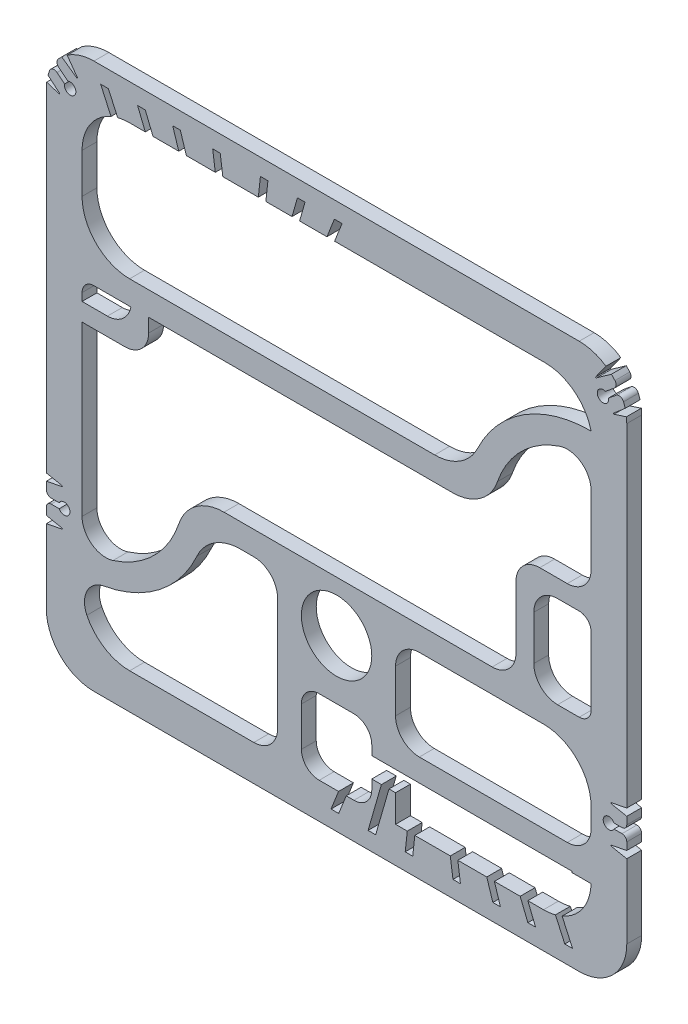
SolidWorks part; units mm, degrees
ref_plane "Front Plane" through (0, 0, 0) normal (0, 0, 1) x (1, 0, 0)
ref_plane "Top Plane" through (0, 0, 0) normal (0, 1, 0) x (1, 0, 0)
ref_plane "Right Plane" through (0, 0, 0) normal (1, 0, 0) x (0, 0, -1)
sketch "Sketch1" plane through (0, 0, 0) normal (0, 0, 1) x (1, 0, 0)
  line L0 (44.642, 21.8842) -> (44.642, 18.0742) construction
  line L1 (-10.1934, 21.8842) -> (51.7832, 21.8842)
  line L2 (-10.1934, 21.8842) -> (-10.1934, -36.406)
  line L3 (-10.1934, -36.406) -> (51.7832, -36.406)
  line L4 (51.7832, 21.8842) -> (51.7832, -36.406)
  line L5 (47.9732, -32.596) -> (-6.3834, -32.596)
  line L6 (47.9732, -32.596) -> (47.9732, 18.0742)
  line L7 (47.9732, 18.0742) -> (-6.3834, 18.0742)
  line L8 (-6.3834, -32.596) -> (-6.3834, 18.0742)
  line L9 (44.642, 19.9792) -> (-35.1587, 19.9792) construction
  line L10 (-6.3834, -31.0517) -> (-10.1934, -31.0517) construction
  line L11 (-8.2884, -31.0517) -> (-8.2884, 6.9585) construction
  line L12 (20.6521, 19.9792) -> (21.1982, 19.9792) construction
  line L14 (3.0779, -32.596) -> (3.0779, -36.406) construction
  line L15 (3.0779, -34.501) -> (37.3423, -34.501) construction
  line L16 (47.9732, -22.563) -> (47.9732, 12.9942) construction
  line L17 (51.7832, 15.2205) -> (47.9732, 15.2205) construction
  line L18 (49.8782, 15.2205) -> (49.8782, -0.9437) construction
  line L20 (20.9378, -34.501) -> (20.3916, -34.501) construction
  line L21 (-6.3834, 8.0412) -> (-6.3834, -27.516) construction
  dimension "D1" = 3.81
  dimension "D2" = 3.81
extrude "Boss-Extrude1" add sketch "Sketch1" along normal blind 1.5875
sketch "Sketch2" plane through (0, 0, 0) normal (0, 0, -1) x (-1, 0, 0)
  line L0 (-47.9732, -32.596) -> (-47.9732, 18.0742) construction
  line L1 (-34.8696, 3.653) -> (6.3834, 3.653)
  line L2 (-47.9732, 3.653) -> (-47.9732, 0.8076)
  line L3 (-37.4096, 1.113) -> (6.3834, 1.113)
  line L4 (6.3834, 3.653) -> (6.3834, 1.113)
  line L5 (6.3834, 18.0742) -> (6.3834, -32.596) construction
  line L6 (-33.4496, 1.113) -> (-36.4496, 1.113) construction
  line L7 (1.2504, -12.887) -> (-36.4496, -12.887) construction
  line L8 (-47.9732, -15.427) -> (-6.8239, -15.427)
  line L9 (-47.9732, -15.427) -> (-47.9732, -12.887)
  line L10 (-47.9732, -12.887) -> (-4.5259, -12.887)
  line L11 (1.357, -21.2563) -> (14.2432, -21.2563) construction
  line L12 (6.3834, -23.7963) -> (6.3834, -26.3363)
  line L13 (-47.9732, 14.2166) -> (-47.9732, 11.6766)
  arc A0 (-47.9732, 11.6766) -> (-37.4096, 1.113) centre (-47.9732, 1.113) cw
  arc A1 (-47.9732, 14.2166) -> (-34.8696, 3.653) centre (-47.9732, 0.8076) cw
  arc A2 (6.3834, -23.7963) -> (-4.5259, -12.887) centre (6.3834, -12.887) cw
  arc A3 (-6.8239, -15.427) -> (6.3834, -26.3363) centre (6.3834, -12.887) ccw
  circle A5 centre (1.357, -18.2591) radius 2.9972 construction
  line M5 (-47.9732, -32.596) -> (-47.9732, 18.0742)
  line M7 (6.3834, 18.0742) -> (6.3834, -32.596)
  dimension "D5" = 2.54
  dimension "D1" = 2.54
  dimension "D2" = 2.54
  dimension "D3" = 2.54
  dimension "D4" = 2.54
  dimension "D6" = 2.54
  dimension "D7" = 2.54
extrude "Boss-Extrude2" add sketch "Sketch2" against normal up to surface (1.5875 mm away) contours A1 A0 L3 L1 M5 M7 | L10 L8 M5 M7 region at (14.2431, 3.0939, 0) region at (-5.8234, -25.0663, 0) up to face at (20.7949, -7.2609, 1.5875)
sketch "Sketch3" plane through (0, 0, 0) normal (0, 0, -1) x (-1, 0, 0)
  line L0 (-47.9732, -1.1649) -> (-39.9496, -1.1649)
  line L1 (-47.9732, -12.887) -> (-47.9732, 11.6766) construction
  line L2 (-39.9496, -4.387) -> (-39.9496, -11.387) construction
  line L3 (-39.9496, -1.1649) -> (-39.9496, -12.887)
  line L4 (-47.9732, -12.887) -> (-4.5259, -12.887) construction
  line L5 (-39.9496, -12.887) -> (-41.8546, -12.887)
  line L6 (-41.8546, -12.887) -> (-41.8546, -3.0699)
  line L7 (-41.8546, -3.0699) -> (-47.9732, -3.0699)
  line L8 (-47.9732, -3.0699) -> (-47.9732, -1.1649)
  line L9 (-42.9468, 0.7401) -> (-53.4831, 0.7401) construction
  line L10 (-0.7296, 1.113) -> (-0.7296, -2.887)
  line L11 (-37.4096, 1.113) -> (6.3834, 1.113) construction
  line L12 (-1.9996, -2.887) -> (1.2504, -2.887) construction
  line L13 (-0.7296, -2.887) -> (6.3834, -2.887)
  line L14 (6.3834, 1.113) -> (6.3834, -23.7963) construction
  line L15 (6.3834, -2.887) -> (6.3834, -0.982)
  line L16 (6.3834, -0.982) -> (1.1754, -0.982)
  line L17 (1.1754, -0.982) -> (1.1754, 1.113)
  line L18 (1.1754, 1.113) -> (-0.7296, 1.113)
  circle A0 centre (-42.9468, 3.7373) radius 2.9972 construction
  dimension "D1" = 1.905
  dimension "D2" = 1.905
  dimension "D3" = 1.905
  dimension "D4" = 1.905
  dimension "D5" = 1.27
  dimension "D6" = 1.905
extrude "Boss-Extrude3" add sketch "Sketch3" against normal up to surface (1.5875 mm away) up to face at (20.8645, -5.9566, 1.5875)
fillet "Fillet1" radius 5.08 4 edges at (51.7832, -36.406, 0.7937) (-10.1934, -36.406, 0.7937) (-10.1934, 21.8842, 0.7937) (51.7832, 21.8842, 0.7937)
fillet "Fillet2" radius 5.08 10 edges at (6.8239, -15.427, 0.7937) (47.9732, -15.427, 0.7937) (47.9732, -32.596, 0.7937) (-6.3834, -32.596, 0.7937) (34.8696, 3.653, 0.7938) (-6.3834, 3.653, 0.7937) (47.9732, 18.0742, 0.7937) (-6.3834, 18.0742, 0.7937) (4.5259, -12.887, 0.7937) (37.4096, 1.113, 0.7938)
fillet "Fillet3" radius 2.54 10 edges at (41.8546, -3.0699, 0.7938) (39.9496, -12.887, 0.7938) (41.8546, -12.887, 0.7938) (39.9496, -1.1649, 0.7938) (47.9732, -1.1649, 0.7938) (-1.1754, -0.982, 0.7938) (0.7296, -2.887, 0.7938) (47.9732, 11.6766, 0.7937) (-6.3834, -26.3363, 0.7937) (-6.3834, -23.7963, 0.7937)
fillet "Fillet4" radius 1.27 3 edges at (47.9732, -12.887, 0.7937) (47.9732, -3.0699, 0.7938) (-6.3834, 1.113, 0.7938)
sketch "Sketch5" plane through (0, 0, 0) normal (0, 0, -1) x (-1, 0, 0)
  line L0 (-42.8932, -15.427) -> (-10.5066, -15.427) construction
  line L1 (-27.0941, -15.427) -> (-14.4957, -15.427)
  line L2 (-27.0941, -15.427) -> (-27.0941, -32.596)
  line L3 (-27.0941, -32.596) -> (-14.4957, -32.596)
  line L4 (-14.4957, -15.427) -> (-14.4957, -32.596)
  line L5 (1.3034, -32.596) -> (-42.8932, -32.596) construction
  line L6 (-24.5541, -18.2972) -> (-27.0941, -18.2972) construction
  line L9 (-17.0357, -18.2972) -> (-14.4957, -18.2972) construction
  circle A1 centre (-20.7949, -18.2972) radius 3.7592 construction
  dimension "D1" = 2.54
extrude "Boss-Extrude4" add sketch "Sketch5" against normal up to surface (1.5875 mm away) up to face at (-4.5227, -0.0173, 1.5875)
sketch "Sketch6" plane through (0, 0, 0) normal (0, 0, -1) x (-1, 0, 0)
  circle A0 centre (-20.7949, -18.2972) radius 3.7592 construction
  circle A1 centre (-20.7949, -18.2972) radius 3.7592
extrude "Cut-Extrude2" cut sketch "Sketch6" against normal up to surface (1.5875 mm away) up to face at (4.768, -24.4396, 1.5875)
sketch "Sketch7" plane through (0, 0, 0) normal (0, 0, -1) x (-1, 0, 0)
  line L0 (-27.0941, -15.427) -> (-27.0941, -32.596) construction
  line L1 (-24.5541, -24.5964) -> (-17.0357, -24.5964)
  line L2 (-24.5541, -24.5964) -> (-24.5541, -32.596)
  line L3 (-24.5541, -32.596) -> (-17.0357, -32.596)
  line L4 (-17.0357, -24.5964) -> (-17.0357, -32.596)
  line L5 (-14.4957, -32.596) -> (-14.4957, -15.427) construction
  line L6 (1.3034, -32.596) -> (-14.4957, -32.596) construction
  line L7 (-20.7949, -22.0564) -> (-6.5424, -22.0564) construction
  line L8 (-20.7949, -22.0564) -> (-20.7949, -21.3452) construction
  circle A0 centre (-20.7949, -18.2972) radius 3.7592 construction
  dimension "D1" = 2.54
  dimension "D2" = 2.54
  dimension "D3" = 2.54
extrude "Cut-Extrude3" cut sketch "Sketch7" against normal up to surface (1.5875 mm away) up to face at (24.5541, -18.2972, 1.5875)
fillet "Fillet5" radius 1.905 4 edges at (24.5541, -32.596, 0.7937) (17.0357, -32.596, 0.7938) (17.0357, -24.5964, 0.7938) (24.5541, -24.5964, 0.7938)
sketch "Sketch8" plane through (0, 0, 0) normal (0, 0, -1) x (-1, 0, 0)
  line L0 (-47.9732, -27.516) -> (-47.9732, -20.507) construction
  line L1 (-47.9732, -25.103) -> (-27.0941, -25.103)
  line L2 (-47.9732, -25.103) -> (-47.9732, -27.643)
  line L3 (-47.9732, -27.643) -> (-27.0941, -27.643)
  line L4 (-27.0941, -25.103) -> (-27.0941, -27.643)
  line L5 (-27.0941, -15.427) -> (-27.0941, -32.596) construction
  line L6 (-45.7916, -27.643) -> (-20.3916, -27.643) construction
  dimension "D1" = 2.54
extrude "Boss-Extrude5" add sketch "Sketch8" against normal up to surface (1.5875 mm away) up to face at (20.7949, -28.5962, 1.5875)
fillet "Fillet6" radius 2.54 5 edges at (27.0941, -15.427, 0.7937) (14.4957, -15.427, 0.7937) (14.4957, -32.596, 0.7937) (27.0941, -25.103, 0.7937) (47.9732, -25.103, 0.7937)
sketch "Sketch4" plane through (0, 0, 0) normal (0, 0, -1) x (-1, 0, 0)
  line L0 (3.2504, -2.887) -> (4.7504, -4.387) construction
  line L1 (4.7504, -11.387) -> (3.2504, -12.887) construction
  line L2 (3.2504, -2.887) -> (4.7504, -4.387)
  line L3 (4.7504, -11.387) -> (3.2504, -12.887)
  line L4 (4.7504, -4.387) -> (4.7504, -11.387) construction
  line L5 (4.7504, -4.387) -> (4.7504, -11.387)
  line L6 (3.2504, -2.887) -> (3.2504, -12.887)
  line L32 (4.2018, 13.1212) -> (4.2018, 15.0262)
  line L33 (4.2018, 15.0262) -> (1.9539, 15.0262)
  line L34 (1.9539, 15.0262) -> (4.2018, 19.9792)
  line L35 (4.2018, 19.9792) -> (3.6556, 19.9792)
  line L36 (3.6556, 19.9792) -> (1.4078, 15.0262)
  line L37 (1.4078, 15.0262) -> (-1.7417, 15.0262)
  line L38 (-1.7417, 15.0262) -> (0.2648, 19.9792)
  line L39 (0.2648, 19.9792) -> (-0.2814, 19.9792)
  line L40 (-0.2814, 19.9792) -> (-2.2879, 15.0262)
  line L41 (-2.2879, 15.0262) -> (-5.0437, 15.0262)
  line L42 (-5.0437, 15.0262) -> (-3.469, 19.9792)
  line L43 (-3.469, 19.9792) -> (-4.0152, 19.9792)
  line L44 (-4.0152, 19.9792) -> (-5.5899, 15.0262)
  line L45 (-5.5899, 15.0262) -> (-8.3965, 15.0262)
  line L46 (-8.3965, 15.0262) -> (-7.7108, 19.9792)
  line L47 (-7.7108, 19.9792) -> (-8.257, 19.9792)
  line L48 (-8.257, 19.9792) -> (-8.9427, 15.0262)
  line L49 (-8.9427, 15.0262) -> (-12.2319, 15.0262)
  line L50 (-12.2319, 15.0262) -> (-12.7781, 19.9792)
  line L51 (-12.7781, 19.9792) -> (-13.3242, 19.9792)
  line L52 (-13.3242, 19.9792) -> (-12.7781, 15.0262)
  line L53 (-12.7781, 15.0262) -> (-15.2926, 15.0262)
  line L54 (-15.2926, 15.0262) -> (-16.7151, 19.9792)
  line L55 (-16.7151, 19.9792) -> (-17.2612, 19.9792)
  line L56 (-17.2612, 19.9792) -> (-15.8388, 15.0262)
  line L57 (-15.8388, 15.0262) -> (-18.6963, 15.0262)
  line L58 (-18.6963, 15.0262) -> (-20.6521, 19.9792)
  line L59 (-20.6521, 19.9792) -> (-21.1982, 19.9792)
  line L60 (-21.1982, 19.9792) -> (-19.2425, 15.0262)
  line L61 (-19.2425, 15.0262) -> (-21.1982, 15.0262)
  line L62 (-21.1982, 15.0262) -> (-21.1982, 13.1212)
  line L63 (-21.1982, 13.1212) -> (4.2018, 13.1212)
  line L64 (4.2018, 13.1212) -> (4.2018, 15.0262) construction
  line L65 (4.2018, 15.0262) -> (1.9539, 15.0262) construction
  line L66 (1.9539, 15.0262) -> (4.2018, 19.9792) construction
  line L67 (4.2018, 19.9792) -> (3.6556, 19.9792) construction
  line L68 (3.6556, 19.9792) -> (1.4078, 15.0262) construction
  line L69 (1.4078, 15.0262) -> (-1.7417, 15.0262) construction
  line L70 (-1.7417, 15.0262) -> (0.2648, 19.9792) construction
  line L71 (0.2648, 19.9792) -> (-0.2814, 19.9792) construction
  line L72 (-0.2814, 19.9792) -> (-2.2879, 15.0262) construction
  line L73 (-2.2879, 15.0262) -> (-5.0437, 15.0262) construction
  line L74 (-5.0437, 15.0262) -> (-3.469, 19.9792) construction
  line L75 (-3.469, 19.9792) -> (-4.0152, 19.9792) construction
  line L76 (-4.0152, 19.9792) -> (-5.5899, 15.0262) construction
  line L77 (-5.5899, 15.0262) -> (-8.3965, 15.0262) construction
  line L78 (-8.3965, 15.0262) -> (-7.7108, 19.9792) construction
  line L79 (-7.7108, 19.9792) -> (-8.257, 19.9792) construction
  line L80 (-8.257, 19.9792) -> (-8.9427, 15.0262) construction
  line L81 (-8.9427, 15.0262) -> (-12.2319, 15.0262) construction
  line L82 (-12.2319, 15.0262) -> (-12.7781, 19.9792) construction
  line L83 (-12.7781, 19.9792) -> (-13.3242, 19.9792) construction
  line L84 (-13.3242, 19.9792) -> (-12.7781, 15.0262) construction
  line L85 (-12.7781, 15.0262) -> (-15.2926, 15.0262) construction
  line L86 (-15.2926, 15.0262) -> (-16.7151, 19.9792) construction
  line L87 (-16.7151, 19.9792) -> (-17.2612, 19.9792) construction
  line L88 (-17.2612, 19.9792) -> (-15.8388, 15.0262) construction
  line L89 (-15.8388, 15.0262) -> (-18.6963, 15.0262) construction
  line L90 (-18.6963, 15.0262) -> (-20.6521, 19.9792) construction
  line L91 (-20.6521, 19.9792) -> (-21.1982, 19.9792) construction
  line L92 (-21.1982, 19.9792) -> (-19.2425, 15.0262) construction
  line L93 (-19.2425, 15.0262) -> (-21.1982, 15.0262) construction
  line L94 (-21.1982, 15.0262) -> (-21.1982, 13.1212) construction
  line L95 (-21.1982, 13.1212) -> (4.2018, 13.1212) construction
  line L96 (-45.7916, -27.643) -> (-45.7916, -29.548)
  line L97 (-45.7916, -29.548) -> (-43.5438, -29.548)
  line L98 (-43.5438, -29.548) -> (-45.7916, -34.501)
  line L99 (-45.7916, -34.501) -> (-45.2455, -34.501)
  line L100 (-45.2455, -34.501) -> (-42.9976, -29.548)
  line L101 (-42.9976, -29.548) -> (-39.8482, -29.548)
  line L102 (-39.8482, -29.548) -> (-41.8546, -34.501)
  line L103 (-41.8546, -34.501) -> (-41.3085, -34.501)
  line L104 (-41.3085, -34.501) -> (-39.302, -29.548)
  line L105 (-39.302, -29.548) -> (-36.5462, -29.548)
  line L106 (-36.5462, -29.548) -> (-38.1208, -34.501)
  line L107 (-38.1208, -34.501) -> (-37.5747, -34.501)
  line L108 (-37.5747, -34.501) -> (-36, -29.548)
  line L109 (-36, -29.548) -> (-33.1934, -29.548)
  line L110 (-33.1934, -29.548) -> (-33.879, -34.501)
  line L111 (-33.879, -34.501) -> (-33.3329, -34.501)
  line L112 (-33.3329, -34.501) -> (-32.6472, -29.548)
  line L113 (-32.6472, -29.548) -> (-29.358, -29.548)
  line L114 (-29.358, -29.548) -> (-28.8118, -34.501)
  line L115 (-28.8118, -34.501) -> (-28.2656, -34.501)
  line L116 (-28.2656, -34.501) -> (-28.8118, -29.548)
  line L117 (-28.8118, -29.548) -> (-26.2973, -29.548)
  line L118 (-26.2973, -29.548) -> (-24.8748, -34.501)
  line L119 (-24.8748, -34.501) -> (-24.3286, -34.501)
  line L120 (-24.3286, -34.501) -> (-25.7511, -29.548)
  line L121 (-25.7511, -29.548) -> (-22.8935, -29.548)
  line L122 (-22.8935, -29.548) -> (-20.9378, -34.501)
  line L123 (-20.9378, -34.501) -> (-20.3916, -34.501)
  line L124 (-20.3916, -34.501) -> (-22.3474, -29.548)
  line L125 (-22.3474, -29.548) -> (-20.3916, -29.548)
  line L126 (-20.3916, -29.548) -> (-20.3916, -27.643)
  line L127 (-20.3916, -27.643) -> (-45.7916, -27.643)
  line L128 (-45.7916, -27.643) -> (-45.7916, -29.548) construction
  line L129 (-45.7916, -29.548) -> (-43.5438, -29.548) construction
  line L130 (-43.5438, -29.548) -> (-45.7916, -34.501) construction
  line L131 (-45.7916, -34.501) -> (-45.2455, -34.501) construction
  line L132 (-45.2455, -34.501) -> (-42.9976, -29.548) construction
  line L133 (-42.9976, -29.548) -> (-39.8482, -29.548) construction
  line L134 (-39.8482, -29.548) -> (-41.8546, -34.501) construction
  line L135 (-41.8546, -34.501) -> (-41.3085, -34.501) construction
  line L136 (-41.3085, -34.501) -> (-39.302, -29.548) construction
  line L137 (-39.302, -29.548) -> (-36.5462, -29.548) construction
  line L138 (-36.5462, -29.548) -> (-38.1208, -34.501) construction
  line L139 (-38.1208, -34.501) -> (-37.5747, -34.501) construction
  line L140 (-37.5747, -34.501) -> (-36, -29.548) construction
  line L141 (-36, -29.548) -> (-33.1934, -29.548) construction
  line L142 (-33.1934, -29.548) -> (-33.879, -34.501) construction
  line L143 (-33.879, -34.501) -> (-33.3329, -34.501) construction
  line L144 (-33.3329, -34.501) -> (-32.6472, -29.548) construction
  line L145 (-32.6472, -29.548) -> (-29.358, -29.548) construction
  line L146 (-29.358, -29.548) -> (-28.8118, -34.501) construction
  line L147 (-28.8118, -34.501) -> (-28.2656, -34.501) construction
  line L148 (-28.2656, -34.501) -> (-28.8118, -29.548) construction
  line L149 (-28.8118, -29.548) -> (-26.2973, -29.548) construction
  line L150 (-26.2973, -29.548) -> (-24.8748, -34.501) construction
  line L151 (-24.8748, -34.501) -> (-24.3286, -34.501) construction
  line L152 (-24.3286, -34.501) -> (-25.7511, -29.548) construction
  line L153 (-25.7511, -29.548) -> (-22.8935, -29.548) construction
  line L154 (-22.8935, -29.548) -> (-20.9378, -34.501) construction
  line L155 (-20.9378, -34.501) -> (-20.3916, -34.501) construction
  line L156 (-20.3916, -34.501) -> (-22.3474, -29.548) construction
  line L157 (-22.3474, -29.548) -> (-20.3916, -29.548) construction
  line L158 (-20.3916, -29.548) -> (-20.3916, -27.643) construction
  line L159 (-20.3916, -27.643) -> (-45.7916, -27.643) construction
  line L263 (4.3288, 12.9942) -> (4.3288, 15.1532)
  line L264 (4.3288, 15.1532) -> (2.151, 15.1532)
  line L265 (2.151, 15.1532) -> (4.3989, 20.1062)
  line L266 (4.3989, 20.1062) -> (3.5738, 20.1062)
  line L267 (3.5738, 20.1062) -> (1.3259, 15.1532)
  line L268 (1.3259, 15.1532) -> (-1.5532, 15.1532)
  line L269 (-1.5532, 15.1532) -> (0.4532, 20.1062)
  line L270 (0.4532, 20.1062) -> (-0.367, 20.1062)
  line L271 (-0.367, 20.1062) -> (-2.3735, 15.1532)
  line L272 (-2.3735, 15.1532) -> (-4.8701, 15.1532)
  line L273 (-4.8701, 15.1532) -> (-3.2954, 20.1062)
  line L274 (-3.2954, 20.1062) -> (-4.1081, 20.1062)
  line L275 (-4.1081, 20.1062) -> (-5.6828, 15.1532)
  line L276 (-5.6828, 15.1532) -> (-8.2507, 15.1532)
  line L277 (-8.2507, 15.1532) -> (-7.565, 20.1062)
  line L278 (-7.565, 20.1062) -> (-8.3676, 20.1062)
  line L279 (-8.3676, 20.1062) -> (-9.0533, 15.1532)
  line L280 (-9.0533, 15.1532) -> (-12.1181, 15.1532)
  line L281 (-12.1181, 15.1532) -> (-12.6643, 20.1062)
  line L282 (-12.6643, 20.1062) -> (-13.466, 20.1062)
  line L283 (-13.466, 20.1062) -> (-12.9198, 15.1532)
  line L284 (-12.9198, 15.1532) -> (-15.1969, 15.1532)
  line L285 (-15.1969, 15.1532) -> (-16.6194, 20.1062)
  line L286 (-16.6194, 20.1062) -> (-17.4298, 20.1062)
  line L287 (-17.4298, 20.1062) -> (-16.0074, 15.1532)
  line L288 (-16.0074, 15.1532) -> (-18.6099, 15.1532)
  line L289 (-18.6099, 15.1532) -> (-20.5657, 20.1062)
  line L290 (-20.5657, 20.1062) -> (-21.3849, 20.1062)
  line L291 (-21.3849, 20.1062) -> (-19.4292, 15.1532)
  line L292 (-19.4292, 15.1532) -> (-21.3252, 15.1532)
  line L293 (-21.3252, 15.1532) -> (-21.3252, 12.9942)
  line L294 (-21.3252, 12.9942) -> (4.3288, 12.9942)
  line L295 (-45.9186, -27.516) -> (-45.9186, -29.675)
  line L296 (-45.9186, -29.675) -> (-43.7409, -29.675)
  line L297 (-43.7409, -29.675) -> (-45.9887, -34.628)
  line L298 (-45.9887, -34.628) -> (-45.1636, -34.628)
  line L299 (-45.1636, -34.628) -> (-42.9158, -29.675)
  line L300 (-42.9158, -29.675) -> (-40.0367, -29.675)
  line L301 (-40.0367, -29.675) -> (-42.0431, -34.628)
  line L302 (-42.0431, -34.628) -> (-41.2229, -34.628)
  line L303 (-41.2229, -34.628) -> (-39.2164, -29.675)
  line L304 (-39.2164, -29.675) -> (-36.7198, -29.675)
  line L305 (-36.7198, -29.675) -> (-38.2945, -34.628)
  line L306 (-38.2945, -34.628) -> (-37.4818, -34.628)
  line L307 (-37.4818, -34.628) -> (-35.9071, -29.675)
  line L308 (-35.9071, -29.675) -> (-33.3392, -29.675)
  line L309 (-33.3392, -29.675) -> (-34.0248, -34.628)
  line L310 (-34.0248, -34.628) -> (-33.2222, -34.628)
  line L311 (-33.2222, -34.628) -> (-32.5366, -29.675)
  line L312 (-32.5366, -29.675) -> (-29.4717, -29.675)
  line L313 (-29.4717, -29.675) -> (-28.9256, -34.628)
  line L314 (-28.9256, -34.628) -> (-28.1239, -34.628)
  line L315 (-28.1239, -34.628) -> (-28.67, -29.675)
  line L316 (-28.67, -29.675) -> (-26.3929, -29.675)
  line L317 (-26.3929, -29.675) -> (-24.9705, -34.628)
  line L318 (-24.9705, -34.628) -> (-24.16, -34.628)
  line L319 (-24.16, -34.628) -> (-25.5825, -29.675)
  line L320 (-25.5825, -29.675) -> (-22.9799, -29.675)
  line L321 (-22.9799, -29.675) -> (-21.0242, -34.628)
  line L322 (-21.0242, -34.628) -> (-20.205, -34.628)
  line L323 (-20.205, -34.628) -> (-22.1607, -29.675)
  line L324 (-22.1607, -29.675) -> (-20.2646, -29.675)
  line L325 (-20.2646, -29.675) -> (-20.2646, -27.516)
  line L326 (-20.2646, -27.516) -> (-45.9186, -27.516)
  dimension "D1" = 0
  dimension "D2" = 0
  dimension "D3" = 0.127
  dimension "D4" = 0.127
extrude "Cut-Extrude1" cut sketch "Sketch4" against normal up to surface (1.5875 mm away) up to face at (37.2819, -20.5167, 1.5875)
sketch "Sketch9" plane through (0, 0, 0) normal (0, 0, -1) x (-1, 0, 0)
  circle A0 centre (-49.2432, 18.0742) radius 0.6096 construction
  circle A1 centre (7.6534, 18.0742) radius 0.6096 construction
  circle A2 centre (8.2884, -21.0912) radius 0.6096 construction
  circle A3 centre (-49.8782, -21.0912) radius 0.6096 construction
  circle A4 centre (-49.2432, 18.0742) radius 0.6096
  circle A5 centre (7.6534, 18.0742) radius 0.6096
  circle A6 centre (8.2884, -21.0912) radius 0.6096
  circle A7 centre (-49.8782, -21.0912) radius 0.6096
extrude "Cut-Extrude4" cut sketch "Sketch9" against normal up to surface (1.5875 mm away) up to face at (31.4097, -31.792, 1.5875)
sketch "Sketch10" plane through (0, 0, 1.5875) normal (0, 0, 1) x (1, 0, 0)
  line L0 (-6.8849, 19.4812) -> (-7.9722, 21.0034) construction
  line L1 (-8.5477, 20.5474) -> (-6.9558, 19.4104) construction
  line L2 (-7.8965, 18.6332) -> (-8.8699, 19.4273) construction
  line L3 (-9.0531, 18.8556) -> (-8.2498, 18.2002) construction
  line L4 (-8.7923, 17.0799) -> (-10.0187, 18.1248) construction
  line L5 (-10.1564, 17.4156) -> (-8.8408, 16.9929) construction
  line L6 (-6.8849, 19.4812) -> (-7.9722, 21.0034)
  line L7 (-8.5477, 20.5474) -> (-6.9558, 19.4104)
  line L8 (-7.8965, 18.6332) -> (-8.8699, 19.4273)
  line L9 (-9.0531, 18.8556) -> (-8.2498, 18.2002)
  line L10 (-8.7923, 17.0799) -> (-10.0187, 18.1248)
  line L11 (-10.1564, 17.4156) -> (-8.8408, 16.9929)
  line L12 (48.4748, 19.4812) -> (49.5621, 21.0034) construction
  line L13 (50.1376, 20.5474) -> (48.5457, 19.4104) construction
  line L14 (49.4864, 18.6332) -> (50.4598, 19.4273) construction
  line L15 (50.643, 18.8556) -> (49.8397, 18.2002) construction
  line L16 (50.3822, 17.0799) -> (51.6086, 18.1248) construction
  line L17 (51.7463, 17.4156) -> (50.4306, 16.9929) construction
  line L18 (50.1273, -19.0774) -> (51.7832, -18.7463) construction
  line L19 (51.7832, -19.5083) -> (50.1273, -19.1771) construction
  line L21 (50.42, -20.8118) -> (51.2752, -20.8118) construction
  line L22 (51.2752, -21.3706) -> (50.42, -21.3706) construction
  line L24 (50.1273, -23.0053) -> (51.7832, -22.6741) construction
  line L25 (51.7832, -23.4361) -> (50.1273, -23.105) construction
  line L26 (-8.5374, -19.0774) -> (-10.1934, -18.7463) construction
  line L27 (-10.1934, -19.5083) -> (-8.5374, -19.1771) construction
  line L29 (-8.8302, -20.8118) -> (-9.6854, -20.8118) construction
  line L30 (-9.6854, -21.3706) -> (-8.8302, -21.3706) construction
  line L32 (-8.5374, -23.0053) -> (-10.1934, -22.6741) construction
  line L33 (-10.1934, -23.4361) -> (-8.5374, -23.105) construction
  line L34 (48.4748, 19.4812) -> (49.5621, 21.0034)
  line L35 (50.1376, 20.5474) -> (48.5457, 19.4104)
  line L36 (49.4864, 18.6332) -> (50.4598, 19.4273)
  line L37 (50.643, 18.8556) -> (49.8397, 18.2002)
  line L38 (50.3822, 17.0799) -> (51.6086, 18.1248)
  line L39 (51.7463, 17.4156) -> (50.4306, 16.9929)
  line L40 (50.1273, -19.0774) -> (51.7832, -18.7463)
  line L41 (51.7832, -19.5083) -> (50.1273, -19.1771)
  line L42 (51.7832, -31.326) -> (51.7832, 16.8042) construction
  line L43 (50.42, -20.8118) -> (51.2752, -20.8118)
  line L44 (51.2752, -21.3706) -> (50.42, -21.3706)
  line L45 (51.7832, -23.4361) -> (51.7832, -22.6741)
  line L46 (50.1273, -23.0053) -> (51.7832, -22.6741)
  line L47 (51.7832, -23.4361) -> (50.1273, -23.105)
  line L48 (-8.5374, -19.0774) -> (-10.1934, -18.7463)
  line L49 (-10.1934, -19.5083) -> (-8.5374, -19.1771)
  line L50 (-10.1934, -20.3038) -> (-10.1934, -21.8786)
  line L51 (-8.8302, -20.8118) -> (-9.6854, -20.8118)
  line L52 (-9.6854, -21.3706) -> (-8.8302, -21.3706)
  line L53 (51.7832, -19.5083) -> (51.7832, -18.7463)
  line L54 (-8.5374, -23.0053) -> (-10.1934, -22.6741)
  line L55 (-10.1934, -23.4361) -> (-8.5374, -23.105)
  line L56 (-10.1934, 16.8042) -> (-10.1934, -31.326) construction
  line L57 (-10.1934, -18.7463) -> (-10.1934, -19.5083)
  line L58 (-10.1934, -22.6741) -> (-10.1934, -23.4361)
  line L59 (51.7832, -21.8786) -> (51.7832, -20.3038)
  arc A0 (-6.9558, 19.4104) -> (-6.8849, 19.4812) centre (-6.9263, 19.4517) ccw construction
  arc A1 (-8.9305, 20.1561) -> (-8.8699, 19.4273) centre (-8.5488, 19.821) ccw construction
  arc A2 (-9.0531, 18.8556) -> (-9.8477, 18.6461) centre (-9.3742, 18.462) ccw construction
  arc A4 (-8.8408, 16.9929) -> (-8.7923, 17.0799) centre (-8.8252, 17.0412) ccw construction
  arc A5 (-6.9558, 19.4104) -> (-6.8849, 19.4812) centre (-6.9263, 19.4517) ccw
  arc A6 (-8.9305, 20.1561) -> (-8.8699, 19.4273) centre (-8.5488, 19.821) ccw
  arc A7 (-9.0531, 18.8556) -> (-9.8477, 18.6461) centre (-9.3742, 18.462) ccw
  arc A8 (-10.0187, 18.1248) -> (-10.1564, 17.4156) centre (-5.1134, 16.8042) ccw
  arc A9 (-8.8408, 16.9929) -> (-8.7923, 17.0799) centre (-8.8252, 17.0412) ccw
  arc A10 (-5.1134, 21.8842) -> (-10.1934, 16.8042) centre (-5.1134, 16.8042) ccw construction
  circle A11 centre (-7.6534, 18.0742) radius 0.6096 construction
  arc A12 (-7.9722, 21.0034) -> (-8.5477, 20.5474) centre (-5.1134, 16.8042) ccw
  arc A13 (-7.8965, 18.6332) -> (-8.2498, 18.2002) centre (-7.6534, 18.0742) ccw
  arc A14 (-8.9305, 20.1561) -> (-9.8477, 18.6461) centre (-5.1134, 16.8042) ccw
  arc A15 (48.4748, 19.4812) -> (48.5457, 19.4104) centre (48.5162, 19.4517) ccw construction
  arc A17 (50.4598, 19.4273) -> (50.5204, 20.1561) centre (50.1387, 19.821) ccw construction
  arc A18 (51.4375, 18.6461) -> (50.643, 18.8556) centre (50.9641, 18.462) ccw construction
  arc A20 (50.3822, 17.0799) -> (50.4306, 16.9929) centre (50.4151, 17.0412) ccw construction
  arc A21 (50.1273, -19.0774) -> (50.1273, -19.1771) centre (50.1373, -19.1273) ccw construction
  arc A22 (51.2752, -20.8118) -> (51.7832, -20.3038) centre (51.2752, -20.3038) ccw construction
  arc A23 (51.7832, -21.8786) -> (51.2752, -21.3706) centre (51.2752, -21.8786) ccw construction
  arc A24 (50.1273, -23.0053) -> (50.1273, -23.105) centre (50.1373, -23.0551) ccw construction
  arc A25 (-8.5374, -19.1771) -> (-8.5374, -19.0774) centre (-8.5474, -19.1273) ccw construction
  arc A26 (-10.1934, -20.3038) -> (-9.6854, -20.8118) centre (-9.6854, -20.3038) ccw construction
  arc A27 (-9.6854, -21.3706) -> (-10.1934, -21.8786) centre (-9.6854, -21.8786) ccw construction
  arc A28 (-8.5374, -23.105) -> (-8.5374, -23.0053) centre (-8.5474, -23.0551) ccw construction
  arc A29 (48.4748, 19.4812) -> (48.5457, 19.4104) centre (48.5162, 19.4517) ccw
  arc A30 (50.1376, 20.5474) -> (49.5621, 21.0034) centre (46.7032, 16.8042) ccw
  arc A31 (50.4598, 19.4273) -> (50.5204, 20.1561) centre (50.1387, 19.821) ccw
  arc A32 (51.4375, 18.6461) -> (50.643, 18.8556) centre (50.9641, 18.462) ccw
  arc A33 (51.4375, 18.6461) -> (50.5204, 20.1561) centre (46.7032, 16.8042) ccw
  arc A34 (50.3822, 17.0799) -> (50.4306, 16.9929) centre (50.4151, 17.0412) ccw
  arc A35 (50.1273, -19.0774) -> (50.1273, -19.1771) centre (50.1373, -19.1273) ccw
  arc A36 (51.2752, -20.8118) -> (51.7832, -20.3038) centre (51.2752, -20.3038) ccw
  arc A37 (51.7832, -21.8786) -> (51.2752, -21.3706) centre (51.2752, -21.8786) ccw
  arc A38 (50.1273, -23.0053) -> (50.1273, -23.105) centre (50.1373, -23.0551) ccw
  arc A39 (-8.5374, -19.1771) -> (-8.5374, -19.0774) centre (-8.5474, -19.1273) ccw
  arc A40 (-10.1934, -20.3038) -> (-9.6854, -20.8118) centre (-9.6854, -20.3038) ccw
  arc A41 (-9.6854, -21.3706) -> (-10.1934, -21.8786) centre (-9.6854, -21.8786) ccw
  arc A42 (-8.5374, -23.105) -> (-8.5374, -23.0053) centre (-8.5474, -23.0551) ccw
  circle A43 centre (-8.2884, -21.0912) radius 0.6096 construction
  arc A44 (-8.8302, -20.8118) -> (-8.8302, -21.3706) centre (-8.2884, -21.0912) ccw
  circle A45 centre (49.8782, -21.0912) radius 0.6096 construction
  arc A46 (50.42, -21.3706) -> (50.42, -20.8118) centre (49.8782, -21.0912) ccw
  circle A47 centre (49.2432, 18.0742) radius 0.6096 construction
  arc A48 (51.7832, 16.8042) -> (46.7032, 21.8842) centre (46.7032, 16.8042) ccw construction
  arc A49 (49.8397, 18.2002) -> (49.4864, 18.6332) centre (49.2432, 18.0742) ccw
  arc A50 (51.7463, 17.4156) -> (51.6086, 18.1248) centre (46.7032, 16.8042) ccw
extrude "Slots for carbon" cut sketch "Sketch10" against normal through all
